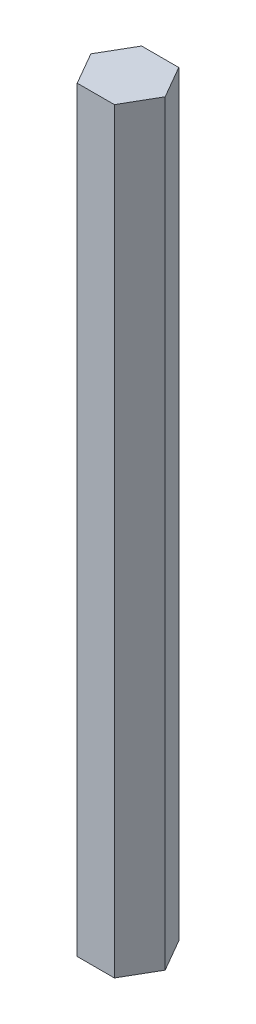
SolidWorks part; units mm, degrees
material "6061-T6 (SS)"
ref_plane "Front" through (0, 0, 0) normal (0, 0, 1) x (1, 0, 0)
ref_plane "Top" through (0, 0, 0) normal (0, 1, 0) x (1, 0, 0)
ref_plane "Right" through (0, 0, 0) normal (1, 0, 0) x (0, 0, -1)
sketch "Sketch1" plane through (0, 0, 0) normal (0, 1, 0) x (1, 0, 0)
  line L1 (7.3323, 0) -> (3.6662, 6.35)
  line L2 (3.6662, 6.35) -> (-3.6662, 6.35)
  line L3 (-3.6662, 6.35) -> (-7.3323, 0)
  line L4 (-7.3323, 0) -> (-3.6662, -6.35)
  line L5 (-3.6662, -6.35) -> (3.6662, -6.35)
  line L6 (3.6662, -6.35) -> (7.3323, 0)
  circle A0 centre (0, 0) radius 6.35 construction
  dimension "D1" = 12.7
extrude "Boss-Extrude1" add sketch "Sketch1" along normal blind 149.225
ref_axis "Axis1" through (0, 50, 0) along (0, -1, 0)
